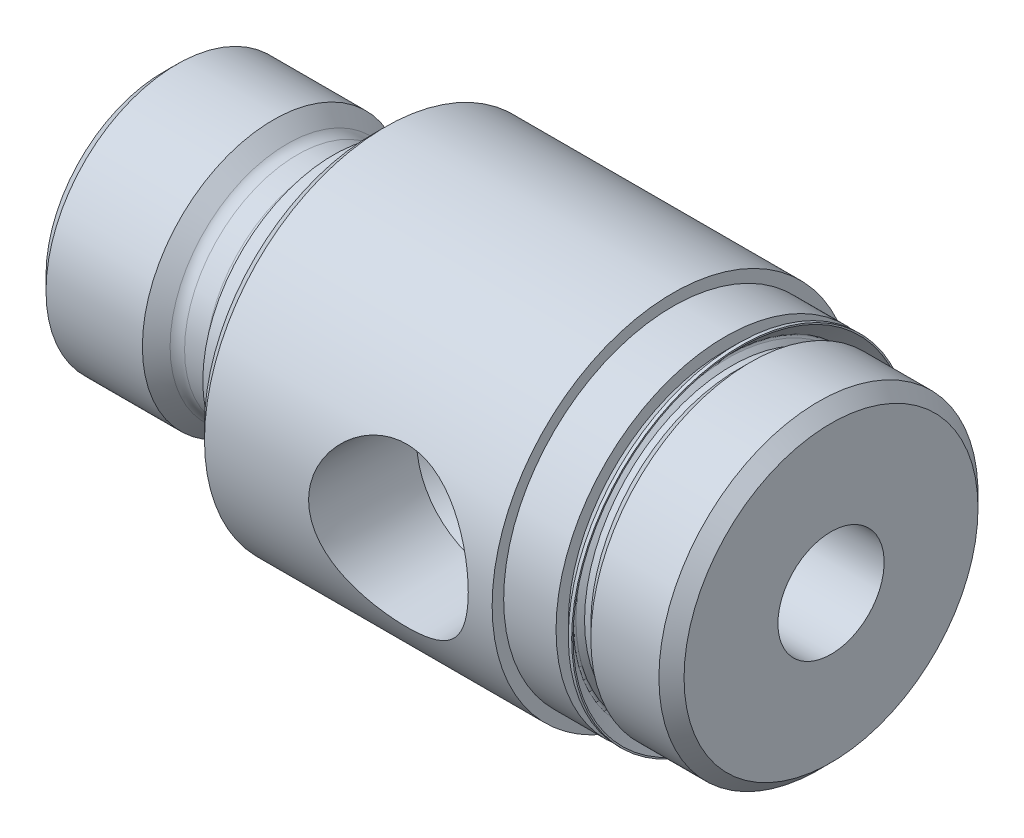
SolidWorks part; units mm, degrees
material "6061-T6 (SS)"
ref_plane "Front Plane" through (0, 0, 0) normal (0, 0, 1) x (1, 0, 0)
ref_plane "Top Plane" through (0, 0, 0) normal (0, 1, 0) x (1, 0, 0)
ref_plane "Right Plane" through (0, 0, 0) normal (1, 0, 0) x (0, 0, -1)
sketch "Sketch1" plane through (0, 0, 0) normal (0, 0, 1) x (1, 0, 0)
  line L0 (0, 0) -> (0, 7.098)
  line L1 (0, 7.098) -> (0.8395, 7.9375)
  line L2 (0.8395, 7.9375) -> (6.6816, 7.9375)
  line L3 (6.6816, 7.9375) -> (7.5202, 7.0965)
  line L4 (8.1407, 6.8389) -> (9.4361, 6.8389)
  line L5 (10.3124, 7.7152) -> (10.3124, 7.9057)
  line L6 (10.3124, 7.9057) -> (12.7, 7.9057)
  line L7 (12.7, 7.9057) -> (12.7, 0)
  line L8 (12.7, 0) -> (0, 0)
  line L9 (12.7, 0) -> (0, 0) construction
  arc A0 (7.5202, 7.0965) -> (8.1407, 6.8389) centre (8.1407, 7.7152) ccw
  arc A1 (9.4361, 6.8389) -> (10.3124, 7.7152) centre (9.4361, 7.7152) ccw
revolve "Revolve1" add sketch "Sketch1" angle 360 about L9 reverse direction yes
cosmetic thread "Cosmetic Thread1" parameters "D1"=7.5202, "D2"=14.1961
sketch "Sketch2" plane through (0, 0, 0) normal (0, 0, 1) x (1, 0, 0)
  line L0 (12.7, 0) -> (12.7, 10.1918)
  line L1 (12.7, 10.1918) -> (13.462, 10.9537)
  line L2 (13.462, 10.9537) -> (34.0741, 10.9537)
  line L3 (34.0741, 10.9537) -> (34.0741, 8.9091)
  line L4 (34.0741, 8.9091) -> (34.8361, 8.9091)
  line L5 (34.8361, 8.9091) -> (35.5981, 9.671)
  line L6 (35.5981, 9.671) -> (39.7256, 9.671)
  line L7 (39.7256, 9.671) -> (40.4876, 8.9091)
  line L8 (40.4876, 8.9091) -> (40.4876, 0)
  line L9 (40.4876, 0) -> (12.7, 0)
  line L10 (40.4876, 0) -> (12.7, 0) construction
revolve "Revolve2" add sketch "Sketch2" angle 360 about L10 reverse direction yes
sketch "Sketch3" plane through (0, 0, 0) normal (0, 0, 1) x (1, 0, 0)
  line L0 (0, 0) -> (0, 3.4735)
  line L1 (0, 3.4735) -> (0.254, 3.2195)
  line L2 (0.254, 3.2195) -> (40.4876, 3.2195)
  line L3 (40.4876, 3.2195) -> (40.4876, 0)
  line L4 (40.4876, 0) -> (0, 0)
  line L5 (40.4876, 0) -> (0, 0) construction
revolve "Cut-Revolve1" cut sketch "Sketch3" angle 360 about L5 reverse direction yes
sketch "Sketch4" plane through (0, 0, 0) normal (0, 0, 1) x (1, 0, 0)
  line L0 (30.8991, 15.3353) -> (30.8991, 10.2553)
  line L1 (30.8991, 10.2553) -> (34.0741, 10.2553)
  line L2 (34.0741, 10.2553) -> (34.0741, 15.3353)
  line L3 (34.0741, 15.3353) -> (30.8991, 15.3353)
  line L4 (34.0741, 0) -> (30.8991, 0) construction
revolve "Cut-Revolve2" cut sketch "Sketch4" angle 360 about L4 reverse direction yes
ref_plane "Plane1" through (11.9126, 0, 0) normal (1, 0, 0) x (0, 0, -1)
ref_plane "Plane2" through (11.9126, 0, 0) normal (1, 0, 0) x (0, 0, -1)
ref_plane "Plane3" through (0, 0, 0) normal (0, -0.7071, 0.7071) x (1, 0, 0)
ref_plane "Plane4" through (2.3368, 0, 0) normal (1, 0, 0) x (0, 0, -1)
ref_plane "Plane5" through (34.1376, 0, 0) normal (1, 0, 0) x (0, 0, -1)
ref_plane "Plane6" through (12.7, 0, 0) normal (1, 0, 0) x (0, 0, -1)
ref_plane "Plane7" through (34.1376, 0, 0) normal (1, 0, 0) x (0, 0, -1)
sketch "Sketch5" plane through (0, 0, 0) normal (0, 1, 0) x (1, 0, 0)
  line L0 (24.6126, 0) -> (27.7876, 0)
  line L1 (27.7876, 0) -> (27.7876, -3.1375)
  line L2 (27.7876, -3.1375) -> (29.2538, -4.6037)
  line L3 (29.2538, -4.6037) -> (29.4521, -10.9537)
  line L4 (29.4521, -10.9537) -> (24.6126, -10.9537)
  line L5 (24.6126, -10.9537) -> (24.6126, 0)
  line L6 (24.6126, -10.9537) -> (24.6126, 0) construction
revolve "Cut-Revolve3" cut sketch "Sketch5" angle 360 about L6 reverse direction yes
cosmetic thread "Cosmetic Thread2" parameters "D1"=3.81, "D2"=10.287
sketch "Sketch6" plane through (0, 0, 0) normal (0, 0, 1) x (1, 0, 0)
  line L0 (34.0741, 9.512) -> (34.0741, 8.655)
  line L1 (34.0741, 8.655) -> (34.8361, 8.655)
  line L2 (34.8361, 8.655) -> (34.8361, 8.9091)
  line L3 (34.8361, 8.9091) -> (34.4551, 8.9091)
  line L4 (34.4551, 8.9091) -> (34.1966, 9.1676)
  line L5 (34.1966, 9.3472) -> (35.0205, 10.1711)
  line L6 (35.0205, 10.1711) -> (35.0205, 10.2552)
  line L7 (35.0205, 10.2552) -> (34.8173, 10.2553)
  line L8 (34.8173, 10.2553) -> (34.0741, 9.512)
  line L9 (34.8361, 0) -> (34.0741, 0) construction
  arc A0 (34.1966, 9.1676) -> (34.1966, 9.3472) centre (34.2864, 9.2574) cw
revolve "Revolve3" add sketch "Sketch6" angle 360 about L9 reverse direction yes
ref_plane "Plane8" through (34.8361, 0, 0) normal (1, 0, 0) x (0, 0, -1)
ref_plane "Plane9" through (12.7, 0, 0) normal (1, 0, 0) x (0, 0, -1)
ref_plane "Plane10" through (10.3124, 0, 0) normal (1, 0, 0) x (0, 0, -1)
ref_plane "Plane11" through (0, 12.7, 0) normal (0, 1, 0) x (1, 0, 0)
ref_plane "Plane12" through (0, -12.7, 0) normal (0, 1, 0) x (1, 0, 0)
ref_plane "Plane13" through (12.7, 0, 0) normal (1, 0, 0) x (0, 0, -1)
ref_plane "Plane14" through (0, 0, 0) normal (0, 0, 1) x (1, 0, 0)
ref_plane "Plane15" through (0, 0, 0) normal (0, 1, 0) x (1, 0, 0)
ref_plane "Plane16" through (0, 0, 0) normal (0, 1, 0) x (1, 0, 0)
ref_plane "Plane17" through (0, 2.032, 0) normal (0, 1, 0) x (1, 0, 0)
ref_plane "Plane18" through (0, 0, 0) normal (1, 0, 0) x (0, 0, -1)
ref_plane "dp1 XY" through (0, 0, 0) normal (0, 0, 1) x (1, 0, 0)
ref_plane "dp1 XZ" through (0, 7.9057, 0) normal (0, -1, 0) x (-1, 0, 0)
ref_plane "dp1 YZ" through (12.7, 0, 0) normal (1, 0, 0) x (0, 0, -1)
ref_axis "dp1 X" through (-80.9, 7.9057, 0) along (1, 0, 0)
ref_axis "dp1 Y" through (12.7, -50, 0) along (0, 1, 0)
ref_axis "dp1 Z" through (12.7, 7.9057, 80.9) along (0, 0, -1)
sketch3d "dp1"
  point P0 (12.7, 7.9057, 0)
ref_plane "dp2 XY" through (0, 0, 0) normal (0, 0, 1) x (1, 0, 0)
ref_plane "dp2 XZ" through (0, -7.9057, 0) normal (0, -1, 0) x (-1, 0, 0)
ref_plane "dp2 YZ" through (12.7, 0, 0) normal (1, 0, 0) x (0, 0, -1)
ref_axis "dp2 X" through (-80.9, -7.9057, 0) along (1, 0, 0)
ref_axis "dp2 Y" through (12.7, -50, 0) along (0, 1, 0)
ref_axis "dp2 Z" through (12.7, -7.9057, 80.9) along (0, 0, -1)
sketch3d "dp2"
  point P0 (12.7, -7.9057, 0)
ref_plane "port XY" through (0, 0, 0) normal (0, 0, 1) x (1, 0, 0)
ref_plane "port XZ" through (0, 0, 0) normal (0, -1, 0) x (-1, 0, 0)
ref_plane "port YZ" through (24.6126, 0, 0) normal (1, 0, 0) x (0, 0, -1)
ref_axis "port X" through (-80.9, 0, 0) along (1, 0, 0)
ref_axis "port Y" through (24.6126, -50, 0) along (0, 1, 0)
ref_axis "port Z" through (24.6126, 0, 80.9) along (0, 0, -1)
sketch3d "port"
  point P0 (24.6126, 0, 0)
ref_plane "rod_guide XY" through (0, 0, 0) normal (1, 0, 0) x (0, 0, -1)
ref_plane "rod_guide XZ" through (0, 0, 0) normal (0, -1, 0) x (-1, 0, 0)
ref_plane "rod_guide YZ" through (0, 0, 0) normal (0, 0, -1) x (-1, 0, 0)
ref_axis "rod_guide X" through (0, 0, 80.9) along (0, 0, -1)
ref_axis "rod_guide Y" through (0, -50, 0) along (0, 1, 0)
ref_axis "rod_guide Z" through (80.9, 0, 0) along (-1, 0, 0)
sketch3d "rod_guide"
  point P0 (0, 0, 0)
ref_plane "s1 XY" through (0, 0, 0) normal (0, 0, 1) x (1, 0, 0)
ref_plane "s1 XZ" through (0, 0, 0) normal (0, -1, 0) x (-1, 0, 0)
ref_plane "s1 YZ" through (10.3124, 0, 0) normal (1, 0, 0) x (0, 0, -1)
ref_axis "s1 X" through (-80.9, 0, 0) along (1, 0, 0)
ref_axis "s1 Y" through (10.3124, -50, 0) along (0, 1, 0)
ref_axis "s1 Z" through (10.3124, 0, 80.9) along (0, 0, -1)
sketch3d "s1"
  point P0 (10.3124, 0, 0)
ref_plane "s2 XY" through (0, 0, 0) normal (0, 0, 1) x (1, 0, 0)
ref_plane "s2 XZ" through (0, 0, 0) normal (0, -1, 0) x (-1, 0, 0)
ref_plane "s2 YZ" through (12.7, 0, 0) normal (1, 0, 0) x (0, 0, -1)
ref_axis "s2 X" through (-80.9, 0, 0) along (1, 0, 0)
ref_axis "s2 Y" through (12.7, -50, 0) along (0, 1, 0)
ref_axis "s2 Z" through (12.7, 0, 80.9) along (0, 0, -1)
sketch3d "s2"
  point P0 (12.7, 0, 0)
ref_plane "t1 XY" through (12.7, 0, 0) normal (1, 0, 0) x (0, 0, -1)
ref_plane "t1 XZ" through (0, 0, 0) normal (0, -1, 0) x (-1, 0, 0)
ref_plane "t1 YZ" through (0, 0, 0) normal (0, 0, -1) x (-1, 0, 0)
ref_axis "t1 X" through (12.7, 0, 80.9) along (0, 0, -1)
ref_axis "t1 Y" through (12.7, -50, 0) along (0, 1, 0)
ref_axis "t1 Z" through (80.9, 0, 0) along (-1, 0, 0)
sketch3d "t1"
  point P0 (12.7, 0, 0)
ref_plane "t111 XY" through (12.7, 0, 0) normal (1, 0, 0) x (0, 0, -1)
ref_plane "t111 XZ" through (0, 0, 0) normal (0, -1, 0) x (-1, 0, 0)
ref_plane "t111 YZ" through (0, 0, 0) normal (0, 0, -1) x (-1, 0, 0)
ref_axis "t111 X" through (12.7, 0, 80.9) along (0, 0, -1)
ref_axis "t111 Y" through (12.7, -50, 0) along (0, 1, 0)
ref_axis "t111 Z" through (80.9, 0, 0) along (-1, 0, 0)
sketch3d "t111"
  point P0 (12.7, 0, 0)
ref_plane "to_foot_bracket XY" through (12.7, 0, 0) normal (1, 0, 0) x (0, 0, -1)
ref_plane "to_foot_bracket XZ" through (0, 0, 0) normal (0, -1, 0) x (-1, 0, 0)
ref_plane "to_foot_bracket YZ" through (0, 0, 0) normal (0, 0, -1) x (-1, 0, 0)
ref_axis "to_foot_bracket X" through (12.7, 0, 80.9) along (0, 0, -1)
ref_axis "to_foot_bracket Y" through (12.7, -50, 0) along (0, 1, 0)
ref_axis "to_foot_bracket Z" through (80.9, 0, 0) along (-1, 0, 0)
sketch3d "to_foot_bracket"
  point P0 (12.7, 0, 0)
ref_plane "to_nut XY" through (10.3124, 0, 0) normal (1, 0, 0) x (0, 0, -1)
ref_plane "to_nut XZ" through (0, 0, 0) normal (0, -1, 0) x (-1, 0, 0)
ref_plane "to_nut YZ" through (0, 0, 0) normal (0, 0, -1) x (-1, 0, 0)
ref_axis "to_nut X" through (10.3124, 0, 80.9) along (0, 0, -1)
ref_axis "to_nut Y" through (10.3124, -50, 0) along (0, 1, 0)
ref_axis "to_nut Z" through (80.9, 0, 0) along (-1, 0, 0)
sketch3d "to_nut"
  point P0 (10.3124, 0, 0)
ref_plane "to_rod XY" through (0, 0, 0) normal (1, 0, 0) x (0, 0, -1)
ref_plane "to_rod XZ" through (0, 0, 0) normal (0, -1, 0) x (-1, 0, 0)
ref_plane "to_rod YZ" through (0, 0, 0) normal (0, 0, -1) x (-1, 0, 0)
ref_axis "to_rod X" through (0, 0, 80.9) along (0, 0, -1)
ref_axis "to_rod Y" through (0, -50, 0) along (0, 1, 0)
ref_axis "to_rod Z" through (80.9, 0, 0) along (-1, 0, 0)
sketch3d "to_rod"
  point P0 (0, 0, 0)
ref_plane "to_screw XY" through (0, 2.032, 0) normal (0, 1, 0) x (1, 0, 0)
ref_plane "to_screw XZ" through (0, 0, -6.0452) normal (0, 0, 1) x (1, 0, 0)
ref_plane "to_screw YZ" through (24.6126, 0, 0) normal (1, 0, 0) x (0, 0, -1)
ref_axis "to_screw X" through (-80.9, 2.032, -6.0452) along (1, 0, 0)
ref_axis "to_screw Y" through (24.6126, 2.032, 50) along (0, 0, -1)
ref_axis "to_screw Z" through (24.6126, 50, -6.0452) along (0, -1, 0)
sketch3d "to_screw"
  point P0 (24.6126, 2.032, -6.0452)
ref_plane "to_trunnion_brackets XY" through (0, 0, 0) normal (0, 1, 0) x (1, 0, 0)
ref_plane "to_trunnion_brackets XZ" through (0, 0, 0) normal (0, 0, 1) x (1, 0, 0)
ref_plane "to_trunnion_brackets YZ" through (11.1252, 0, 0) normal (1, 0, 0) x (0, 0, -1)
ref_axis "to_trunnion_brackets X" through (-80.9, 0, 0) along (1, 0, 0)
ref_axis "to_trunnion_brackets Y" through (11.1252, 0, 50) along (0, 0, -1)
ref_axis "to_trunnion_brackets Z" through (11.1252, 50, 0) along (0, -1, 0)
sketch3d "to_trunnion_brackets"
  point P0 (11.1252, 0, 0)
ref_plane "to_trunnion_brackets1 XY" through (0, 12.7, 0) normal (0, 1, 0) x (1, 0, 0)
ref_plane "to_trunnion_brackets1 XZ" through (0, 0, 0) normal (0, 0, 1) x (1, 0, 0)
ref_plane "to_trunnion_brackets1 YZ" through (11.1252, 0, 0) normal (1, 0, 0) x (0, 0, -1)
ref_axis "to_trunnion_brackets1 X" through (-80.9, 12.7, 0) along (1, 0, 0)
ref_axis "to_trunnion_brackets1 Y" through (11.1252, 12.7, 50) along (0, 0, -1)
ref_axis "to_trunnion_brackets1 Z" through (11.1252, 50, 0) along (0, -1, 0)
sketch3d "to_trunnion_brackets1"
  point P0 (11.1252, 12.7, 0)
ref_plane "to_trunnion_brackets2 XY" through (0, -12.7, 0) normal (0, 1, 0) x (1, 0, 0)
ref_plane "to_trunnion_brackets2 XZ" through (0, 0, 0) normal (0, 0, 1) x (1, 0, 0)
ref_plane "to_trunnion_brackets2 YZ" through (11.1252, 0, 0) normal (1, 0, 0) x (0, 0, -1)
ref_axis "to_trunnion_brackets2 X" through (-80.9, -12.7, 0) along (1, 0, 0)
ref_axis "to_trunnion_brackets2 Y" through (11.1252, -12.7, 50) along (0, 0, -1)
ref_axis "to_trunnion_brackets2 Z" through (11.1252, 50, 0) along (0, -1, 0)
sketch3d "to_trunnion_brackets2"
  point P0 (11.1252, -12.7, 0)
ref_plane "to_tube XY" through (34.8361, 0, 0) normal (1, 0, 0) x (0, 0, -1)
ref_plane "to_tube XZ" through (0, 0, 0) normal (0, -1, 0) x (-1, 0, 0)
ref_plane "to_tube YZ" through (0, 0, 0) normal (0, 0, -1) x (-1, 0, 0)
ref_axis "to_tube X" through (34.8361, 0, 80.9) along (0, 0, -1)
ref_axis "to_tube Y" through (34.8361, -50, 0) along (0, 1, 0)
ref_axis "to_tube Z" through (80.9, 0, 0) along (-1, 0, 0)
sketch3d "to_tube"
  point P0 (34.8361, 0, 0)
